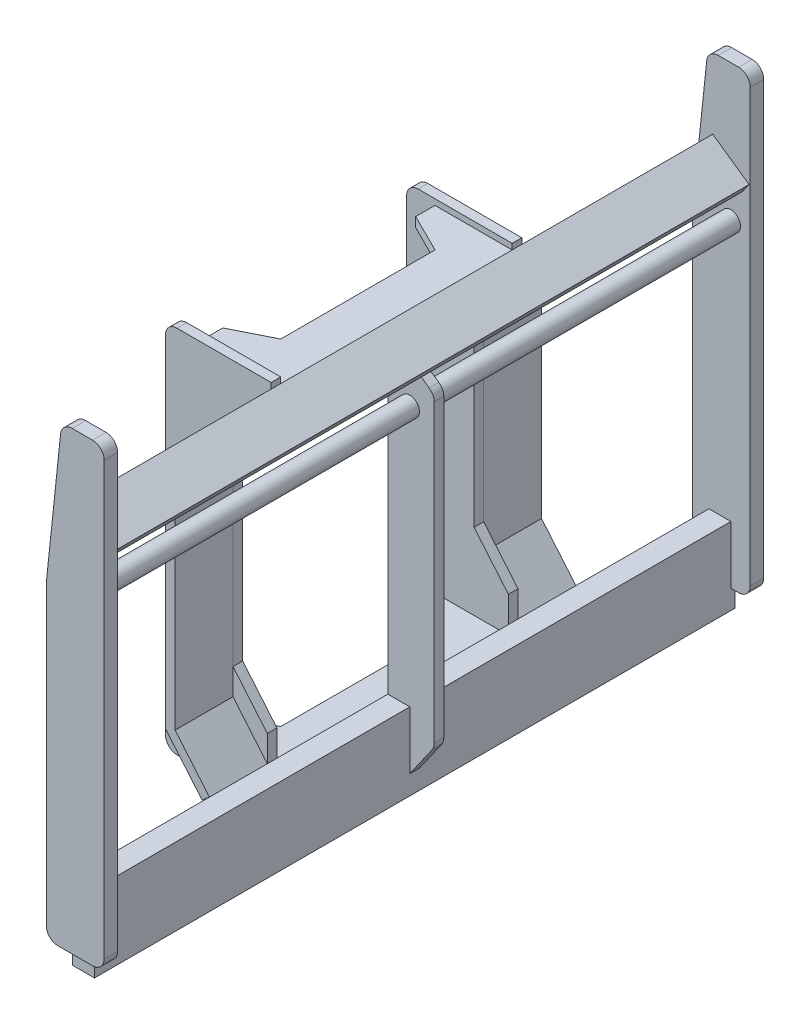
SolidWorks part; units mm, degrees
ref_plane "Front Plane" through (0, 0, 0) normal (0, 0, 1) x (1, 0, 0)
ref_plane "Top Plane" through (0, 0, 0) normal (0, 1, 0) x (1, 0, 0)
ref_plane "Right Plane" through (0, 0, 0) normal (1, 0, 0) x (0, 0, -1)
sketch "Sketch1" plane through (0, 0, 0) normal (0, 0, 1) x (1, 0, 0)
  line L0 (0, 0) -> (0, 1180)
  line L1 (0, 0) -> (-150, 0)
  line L2 (-150, 0) -> (-150, 800)
  line L3 (-150, 800) -> (-110, 1180)
  line L4 (-110, 1180) -> (0, 1180)
  dimension "D1" = 1180
  dimension "D2" = 150
  dimension "D3" = 110
  dimension "D4" = 800
extrude "Boss-Extrude3" add sketch "Sketch1" along normal blind 25 from offset 830 contours L2 L3 L4 L0 L1
extrude "Boss-Extrude4" add sketch "Sketch1<5>" against normal blind 25 from offset 820 separate body offset against normal yes
sketch "Sketch1<5>" plane through (0, 0, 0) normal (0, 0, 1) x (1, 0, 0) same geometry as "Sketch1"
sketch "Sketch2" plane through (0, 0, -820) normal (0, 0, 1) x (1, 0, 0)
  line L0 (-3, 930) -> (-20.2073, 905.4254)
  line L1 (-107, 150) -> (-50, 150)
  line L2 (-107, 150) -> (-107, -50)
  line L3 (-107, -50) -> (-50, -50)
  line L4 (-50, 150) -> (-50, -50)
  line L5 (-3, 930) -> (-97.2025, 995.9613)
  line L6 (-20.2073, 905.4254) -> (-114.4098, 971.3867)
  line L7 (-97.2025, 995.9613) -> (-114.4098, 971.3867)
  line L8 (0, 0) -> (0, 1180) construction
  line L9 (0, 1180) -> (-110, 1180) construction
  line L10 (-150, 0) -> (0, 0) construction
  dimension "D1" = 30
  dimension "D2" = 115
  dimension "D3" = 3
  dimension "D4" = 55
  dimension "D5" = 250
  dimension "D6" = 57
  dimension "D7" = 50
  dimension "D8" = 150
  dimension "D9" = 200
extrude "Boss-Extrude5" add sketch "Sketch2" along normal up to surface (1650 mm away) contours L2 L3 L4 L1 | L6 L7 L5 L0 up to face at (-82, 632, 830)
sketch "Sketch5" plane through (0, 0, 0) normal (0, 0, 1) x (1, 0, 0)
  line L0 (-114.6622, 971.7113) -> (27.907, 861.1961)
  line L1 (27.907, 861.1961) -> (20.0325, 28.6171)
  line L2 (20.0325, 28.6171) -> (-49.6238, -39.7339)
  line L3 (-49.6238, -39.7339) -> (-49.6238, 150.3946)
  line L4 (-49.6238, 150.3946) -> (-108.0663, 150.3946)
  line L5 (-108.0663, 150.3946) -> (-108.0663, 966.5983)
sketch "Sketch6" plane through (0, 0, 0) normal (0, 0, 1) x (1, 0, 0)
  line L0 (-107, 966.1983) -> (13, 882.1734)
  line L1 (13, 882.1734) -> (13, 89.9733)
  line L2 (13, 89.9733) -> (-50, 0)
  line L3 (-50, 150) -> (-50, 0) construction
  line L4 (-50, 0) -> (-50, 150)
  line L5 (-50, 150) -> (-107, 150)
  line L6 (-107, 150) -> (-107, 966.1983)
  line L7 (-20.2073, 905.4254) -> (-114.4098, 971.3867) construction
  dimension "D1" = 120
  dimension "D2" = 0
  dimension "D3" = 150
extrude "Boss-Extrude6" add sketch "Sketch6" along normal mid plane 25 contours L0 L1 L2 L4 L5 L6
sketch "Sketch7" plane through (0, 0, 855) normal (0, 0, 1) x (1, 0, 0)
  line L0 (0, 0) -> (0, 1180) construction
  line L1 (-110, 1180) -> (0, 1180) construction
  circle A0 centre (-50, 825) radius 25
  dimension "D1" = 50
  dimension "D2" = 50
  dimension "D3" = 355
extrude "Cut-Extrude1" cut sketch "Sketch7" against normal through all contours A0
sketch "Sketch9" plane through (0, 0, 855) normal (0, 0, 1) x (1, 0, 0)
  circle A0 centre (-50, 825) radius 25 construction
  circle A1 centre (-50, 825) radius 25
extrude "Boss-Extrude7" add sketch "Sketch9" against normal up to surface (1700 mm away) up to face at (-25, 825, -845)
sketch "Sketch15" plane through (0, 0, 0) normal (0, 0, 1) x (1, 0, 0)
  line L0 (-114.4098, 971.3867) -> (-20.2073, 905.4254) construction
  line L1 (-114.4098, 971.3867) -> (-97.2025, 995.9613) construction
  line L3 (-114.4098, 971.3867) -> (-107, 966.1983)
  line L4 (-114.4098, 971.3867) -> (-97.2025, 995.9613)
  line L5 (-107, 217.93) -> (-107, 150)
  line L6 (-97.2025, 995.9613) -> (-97.2025, 1010.9613)
  line L7 (-97.2025, 1010.9613) -> (-371, 1010.9613)
  line L8 (-371, 1010.9613) -> (-371, 52.9613)
  line L9 (-371, 52.9613) -> (-107, 52.9613)
  line L10 (-107, 52.9613) -> (-107, 150)
  line L11 (-107, 217.93) -> (-196, 323.996)
  line L12 (-196, 323.996) -> (-196, 822.5318)
  line L13 (-196, 822.5318) -> (-107, 902.6677)
  line L14 (-107, 150) -> (-107, 966.1983) construction
  line L15 (-107, 902.6677) -> (-107, 966.1983)
  line L16 (-107, 150) -> (-107, 966.1983) construction
  dimension "D1" = 77
  dimension "D2" = 175
  dimension "D3" = 89
  dimension "D5" = 15
  dimension "D6" = 958
extrude "Boss-Extrude13" add sketch "Sketch15" against normal blind 25 from offset 300 contours L7 L8 L9 L10 L5 L11 L12 L13 L15 L3 L4 L6 offset against normal yes
sketch "Sketch18" plane through (0, 0, -325) normal (0, 0, -1) x (-1, 0, 0)
  line L0 (107, 150) -> (196, 256.0661)
  line L1 (196, 256.0661) -> (196, 859.7532)
  line L2 (196, 859.7532) -> (107, 934.433)
  line L3 (107, 902.6677) -> (107, 966.1983) construction
  line L4 (196, 323.996) -> (196, 822.5318) construction
  dimension "D1" = 130
  dimension "D2" = 140
  dimension "D4" = 0
extrude "Extrude-Thin7" add sketch "Sketch18" along normal blind 150 separate body thin thin type one direction wall 25
sketch "Sketch19" plane through (397.3283, 333.398, 0) normal (0.766, 0.6428, 0) x (0, 0, -1)
  line L4 (325, 809.5955) -> (325, 784.5955)
  line L5 (325, 784.5955) -> (475, 784.5955)
  line L6 (475, 784.5955) -> (475, 809.5955)
  line L7 (475, 809.5955) -> (325, 809.5955)
  line L8 (325, 809.5955) -> (325, 784.5955)
  line L9 (325, 784.5955) -> (475, 784.5955)
  line L10 (475, 784.5955) -> (475, 809.5955)
  line L11 (475, 809.5955) -> (325, 809.5955)
  dimension "D1" = 0
extrude "Boss-Extrude15" add sketch "Sketch19" along normal up to next separate body
mirror "Mirror1" about plane through (0, 0, 0) normal (0, 0, 1) of bodies 115 116 114
ref_plane "Plane6" through (0, 995.9613, 0) normal (0, 1, 0) x (1, 0, 0)
sketch "Sketch21" plane through (0, 995.9613, 0) normal (0, 1, 0) x (1, 0, 0)
  line L0 (-297.2025, 300) -> (-97.2025, 300)
  line L1 (-97.2025, 300) -> (-371, 300) construction
  line L2 (-97.2025, 300) -> (-97.2025, -300)
  line L3 (-97.2025, -300) -> (-297.2025, -300)
  line L4 (-97.2025, -300) -> (-371, -300) construction
  line L5 (-297.2025, -300) -> (-297.2025, -250)
  line L6 (-297.2025, -250) -> (-197.2025, -200)
  line L7 (-197.2025, -200) -> (-197.2025, 200)
  line L9 (-297.2025, 300) -> (-297.2025, 250)
  line L10 (0, 0) -> (-318.6517, 0) construction
  line L11 (-149.8214, 250) -> (-150.8984, 250)
  line L12 (-297.2025, 250) -> (-197.2025, 200)
  dimension "D1" = 50
  dimension "D3" = 100
  dimension "D4" = 200
  dimension "D6" = 400
extrude "Boss-Extrude16" add sketch "Sketch21" against normal blind 25 contours L12 L7 L6 L5 L3 L2 L0 L9
pattern_linear "LPattern3" count 2 spacing 870 along (0, -1, 0) of "Boss-Extrude16"
fillet "Fillet1" radius 30 1 edges at (-371, 52.9613, -312.5)
fillet "Fillet2" radius 30 3 edges at (-150, 0, -837.5) (-150, 0, 837.5) (-371, 52.9613, 312.5)
fillet "Fillet3" radius 30 4 edges at (0, 0, -837.5) (0, 0, 837.5) (-371, 1010.9613, 312.5) (-371, 1010.9613, -312.5)
fillet "Fillet4" radius 30 4 edges at (0, 1180, 837.5) (-110, 1180, 837.5) (0, 1180, -837.5) (-110, 1180, -837.5)
fillet "Fillet5" radius 30 1 edges at (13, 882.1734, 0)
fillet "Fillet6" radius 30 1 edges at (13, 89.9733, 0)
pattern_linear "LPattern1" count 2 spacing 870 along (0, -1, 0) of "Boss-Extrude16"
